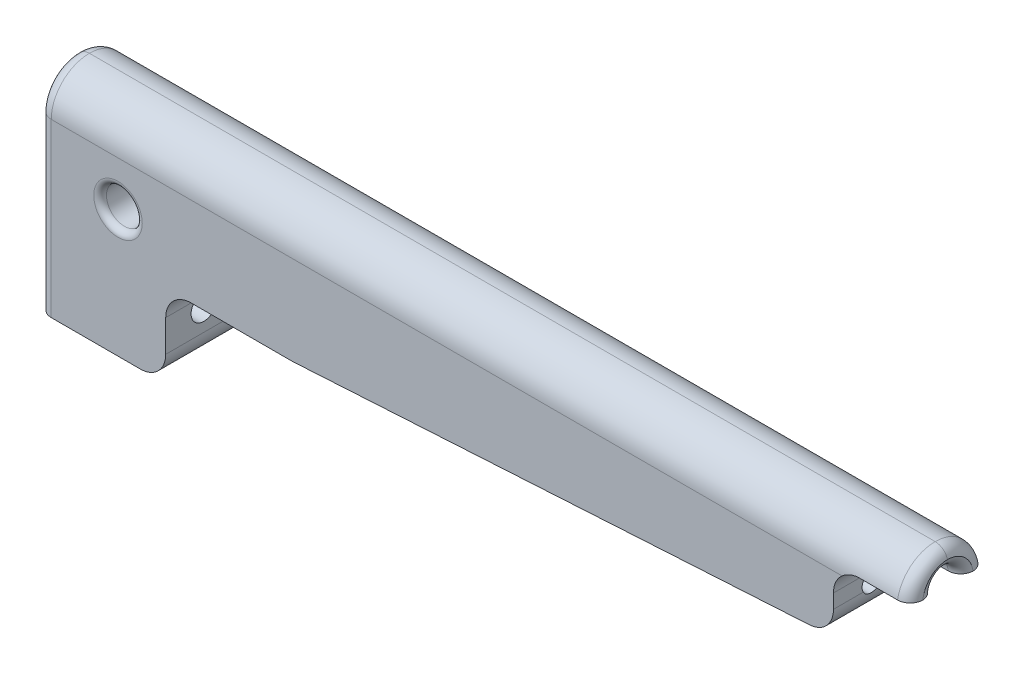
SolidWorks part; units mm, degrees
ref_plane "Front Plane" through (0, 0, 0) normal (0, 0, 1) x (1, 0, 0)
ref_plane "Top Plane" through (0, 0, 0) normal (0, 1, 0) x (1, 0, 0)
ref_plane "Right Plane" through (0, 0, 0) normal (1, 0, 0) x (0, 0, -1)
sketch "Sketch1" plane through (0, 0, 0) normal (0, 0, 1) x (1, 0, 0)
  line L0 (-0.1915, 12.7) -> (-50000.1915, 12.7) construction
  line L1 (25.4, 0) -> (173.99, 0)
  line L2 (0, 0) -> (0, 25.4)
  line L4 (173.99, 0) -> (173.99, 25.4)
  line L5 (173.99, 25.4) -> (0, 25.4)
  line L6 (0, 0) -> (0, -16.51)
  line L7 (0, -16.51) -> (25.4, -16.51)
  line L8 (25.4, -16.51) -> (25.4, 0)
  point P7 (0, 12.7)
  dimension "D1" = 25.4
  dimension "D3" = 16.51
  dimension "D2" = 173.99
  dimension "D4" = 25.4
  dimension "D6" = 25.4
extrude "Boss-Extrude1" add sketch "Sketch1" against normal blind 15.24
fillet "Fillet2" radius 7.62 2 edges at (86.995, 25.4, 0) (86.995, 25.4, -15.24)
sketch "Sketch2" plane through (0, 0, 0) normal (0, 0, 1) x (1, 0, 0)
  line L0 (158.75, 19.05) -> (158.75, 6.35)
  line L2 (25.4, 0) -> (173.99, 0) construction
  line L3 (50.8, 0) -> (153.899, 0)
  line L4 (158.75, 19.05) -> (173.99, 19.05)
  line L5 (0, 17.78) -> (0, -16.51) construction
  line L6 (173.99, 0) -> (173.99, 17.78) construction
  line L7 (173.99, 19.05) -> (173.99, 0)
  line L8 (173.99, 0) -> (153.899, 0)
  line L9 (158.75, 6.35) -> (50.8, 0)
  dimension "D1" = 19.05
  dimension "D2" = 50.8
  dimension "D3" = 15.24
  dimension "D4" = 12.7
extrude "Cut-Extrude1" cut sketch "Sketch2" against normal through all
sketch "Sketch3" plane through (0, 0, 0) normal (0, 0, 1) x (1, 0, 0)
  line L0 (0, 8.89) -> (158.75, 8.89) construction
  line L1 (0, 17.78) -> (0, -16.51) construction
  line L2 (0, 0) -> (0, 17.78) construction
  line L3 (0, 17.78) -> (0, -16.51) construction
  line L4 (158.75, 17.78) -> (158.75, 6.35) construction
  point P6 (15.875, 8.89)
  point P10 (0, 8.89)
  dimension "D1" = 15.875
hole_wizard "9/32 (0.28125) Diameter Hole1" positions "3DSketch1" profile "Sketch4" hole size "9/32" standard "ANSI Inch" end condition through all
sketch3d "3DSketch1"
  point P0 (15.875, 8.89, 0)
sketch "Sketch4" plane through (15.875, 8.89, 0) normal (1, 0, 0) x (0, -1, 0)
  line L0 (0, 0) -> (0, 15.24)
  line L1 (0, 15.24) -> (3.5719, 15.24)
  line L2 (3.5719, 15.24) -> (3.5719, 0)
  line L5 (3.5719, 0) -> (0, 0)
  line L11 (0, -6.35) -> (0, 107.95) construction
  dimension "Thru Hole Dia." = 7.1437
  dimension "Thru Hole Depth" = 15.24
sketch "Sketch5" plane through (158.75, 0, 0) normal (1, 0, 0) x (0, 0, -1)
  line L0 (0, 12.065) -> (15.24, 12.065) construction
  line L1 (0, 17.78) -> (0, 6.35) construction
  line L2 (15.24, 17.78) -> (15.24, 6.35) construction
  line L3 (7.62, 19.05) -> (7.62, 6.35) construction
  line L4 (15.1334, 19.05) -> (0.1066, 19.05) construction
  line L5 (15.24, 6.35) -> (0, 6.35) construction
  point P12 (7.62, 12.065)
hole_wizard "#10-24 Tapped Hole1" positions "3DSketch2" profile "Sketch6" tap size "#10-24" standard "ANSI Inch"
sketch3d "3DSketch2"
  point P0 (158.75, 12.065, -7.62)
sketch "Sketch6" plane through (158.75, 12.065, -7.62) normal (0, 1, 0) x (0, 0, -1)
  line L0 (0, 0) -> (0, 58.2908)
  line L1 (0, 58.2908) -> (1.8986, 57.15)
  line L2 (1.8986, 57.15) -> (1.8986, 0)
  line L5 (1.8986, 0) -> (0, 0)
  line L10 (0, 58.2908) -> (-1.8987, 57.15) construction
  line L11 (0, -6.35) -> (0, 107.95) construction
  dimension "Tap Drill Dia." = 3.7973
  dimension "Tap Drill Depth" = 57.15
  dimension "Drill Angle" = 118
cosmetic thread "Hole Thread1" parameters "D1"=50.8, "D2"=4.826
sketch "Sketch7" plane through (173.99, 0, 0) normal (1, 0, 0) x (0, 0, -1)
  line L0 (15.1334, 19.05) -> (0.1066, 19.05) construction
  circle A0 centre (7.62, 19.05) radius 2.5718
extrude "Cut-Extrude2" cut sketch "Sketch7" against normal blind 6.35 contours A0
fillet "Fillet7" radius 5.08 4 edges at (158.75, 6.35, -7.62) (158.75, 19.05, -7.62) (25.4, 0, -7.62) (25.4, -16.51, -7.62)
fillet "Fillet8" radius 2.54 3 edges at (173.99, 21.6218, -7.62) (173.99, 23.5999, -12.5387) (173.99, 23.5999, -2.7013)
fillet "Fillet9" radius 2.54 1 edges at (167.64, 21.6218, -7.62)
fillet "Fillet10" radius 2.54 4 edges at (0, 0.635, 0) (0, 0.635, -15.24) (0, 23.1682, -13.0082) (0, 23.1682, -2.2318)
fillet "Fillet11" radius 1.27 2 edges at (19.4469, 8.89, 0) (19.4469, 8.89, -15.24)
sketch "Sketch8" plane through (0, 0, 0) normal (-1, 0, 0) x (0, 0, 1)
  line L0 (-7.62, -16.51) -> (-7.62, 22.86) construction
  line L1 (-12.7, -16.51) -> (-2.54, -16.51) construction
  point P0 (-7.62, -6.985)
  dimension "D1" = 15.875
hole_wizard "1/4-20 Tapped Hole1" positions "Sketch10" profile "Sketch9" tap size "1/4-20" standard "ANSI Inch"
sketch "Sketch10" plane through (0, 0, 0) normal (-1, 0, 0) x (0, 0, 1)
  point P0 (-7.62, -6.985)
sketch "Sketch9" plane through (0, -6.985, -7.62) normal (0, 1, 0) x (0, 0, 1)
  line L0 (0, 0) -> (0, 28.9658)
  line L1 (0, 28.9658) -> (2.5527, 27.432)
  line L2 (2.5527, 27.432) -> (2.5527, 0)
  line L5 (2.5527, 0) -> (0, 0)
  line L10 (0, 28.9658) -> (-2.5527, 27.432) construction
  line L11 (0, -6.35) -> (0, 107.95) construction
  dimension "Tap Drill Dia." = 5.1054
  dimension "Tap Drill Depth" = 27.432
  dimension "Drill Angle" = 118
cosmetic thread "Hole Thread2" parameters "D1"=20.32, "D2"=6.35
